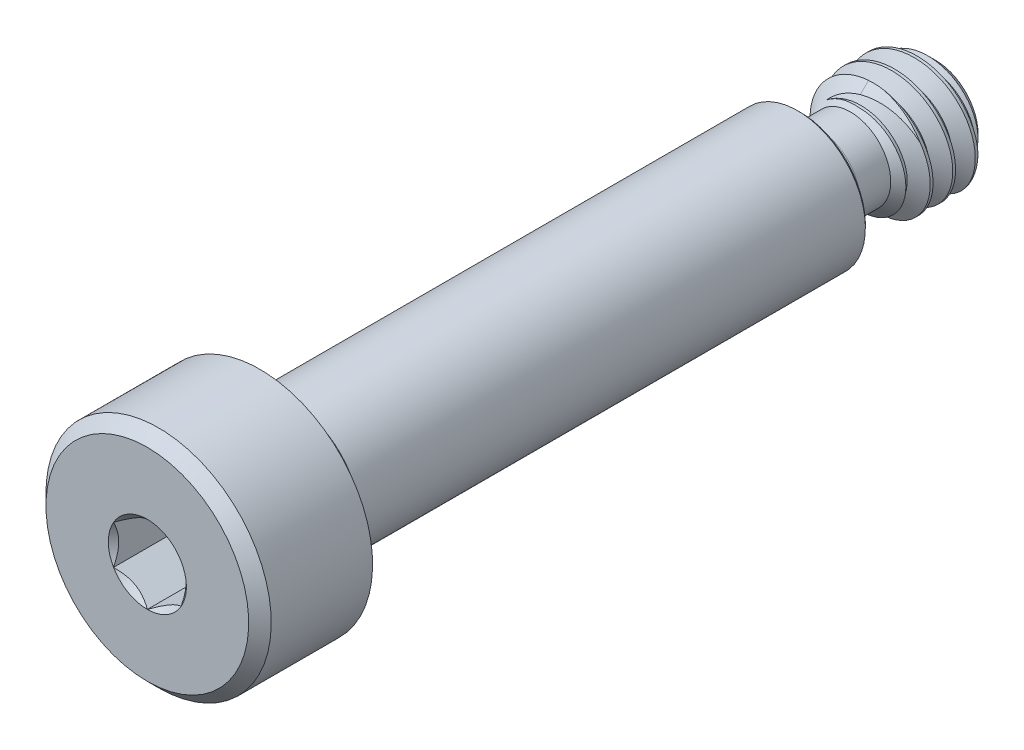
SolidWorks part; units mm, degrees
ref_plane "Front Plane" through (0, 0, 0) normal (0, 0, 1) x (1, 0, 0)
ref_plane "Top Plane" through (0, 0, 0) normal (0, 1, 0) x (1, 0, 0)
ref_plane "Right Plane" through (0, 0, 0) normal (1, 0, 0) x (0, 0, -1)
sketch "Sketch1" plane through (0, 0, 0) normal (1, 0, 0) x (0, 0, -1)
  line L0 (-13.8906, 0) -> (13.8906, 0) construction
  line L1 (-13.8906, 0) -> (-13.8906, 3.9687)
  line L2 (-13.8906, 3.9687) -> (-9.9219, 3.9688)
  line L3 (-9.9219, 3.9688) -> (-9.9219, 2.3813)
  line L4 (-9.9219, 2.3813) -> (9.1281, 2.3813)
  line L5 (9.1281, 2.0828) -> (13.8906, 2.0828)
  line L6 (13.8906, 2.0828) -> (13.8906, 0)
  line L7 (13.841, 2.1687) -> (14.2379, 1.4813) construction
  line L8 (14.2379, 1.4813) -> (14.6348, 2.1687) construction
  line L9 (14.6348, 2.1687) -> (13.841, 2.1687) construction
  line L10 (13.8906, 2.0828) -> (14.5852, 2.0828) construction
  line L11 (14.2379, 2.1687) -> (14.2379, 2.0828) construction
  line L12 (14.2379, 2.0828) -> (14.2379, 1.5672) construction
  line L13 (14.2379, 1.5672) -> (14.2379, 1.4813) construction
  line L14 (14.1883, 1.5672) -> (14.2875, 1.5672)
  line L15 (13.8658, 2.1258) -> (14.61, 2.1258)
  line L16 (14.2875, 1.5672) -> (14.61, 2.1258)
  line L17 (14.1883, 1.5672) -> (13.8658, 2.1258)
  line L18 (13.8906, 0) -> (13.8906, -2.0828) construction
  line L19 (9.1281, -2.3813) -> (9.1281, 0) construction
  line L20 (9.1281, 0) -> (9.1281, 2.3813) construction
  line L21 (-13.8906, 0) -> (-13.8906, -3.9687) construction
  line L22 (9.1281, 2.3813) -> (9.1281, 2.0828)
  line L23 (9.1281, 2.3813) -> (11.8396, 2.3813)
  line L24 (11.8396, 2.3813) -> (10.8807, 1.4224)
  line L25 (10.8807, 1.4224) -> (9.7885, 1.4224)
  arc A0 (9.1281, 2.0828) -> (9.7885, 1.4224) centre (9.7885, 2.0828) ccw
  point P11 (-8.7789, 2.3813)
  point P12 (11.9062, -2.0828)
  point P22 (14.2379, 2.1258)
  point P23 (8.1756, 0)
  point P25 (-8.1756, 0)
  point P26 (-9.9219, -3.9687)
  point P29 (9.1281, -2.3813)
  point P33 (-6.2389, 2.3813)
  point P36 (6.5881, 2.3813)
  dimension "Head Height" = 3.9688
  dimension "Shoulder Diameter" = 4.7625
  dimension "Screw Size Decimal Equivalent" = 4.1656
  dimension "Thread Length" = 4.7625
  dimension "Head Diameter" = 7.9375
  dimension "Undercut Length" = 1.143
  dimension "Pitch" = 0.7937
  dimension "D2" = 0.0992
  dimension "D1" = 1.9844
  dimension "D3" = 5.715
  dimension "D4" = 5.715
  dimension "Shoulder Length" = 19.05
  dimension "Flat OD" = 2.8448
  dimension "Flat" = 1.7526
  dimension "D5" = 45
  dimension "D7" = 2.54
  dimension "D6" = 3.683
sketch "Sketch2" plane through (0, 0, 0) normal (0, 0, 1) x (1, 0, 0)
  line L1 (0, 1.3748) -> (-1.1906, 0.6874)
  line L2 (-1.1906, 0.6874) -> (-1.1906, -0.6874)
  line L3 (-1.1906, -0.6874) -> (0, -1.3748)
  line L4 (0, -1.3748) -> (1.1906, -0.6874)
  line L5 (1.1906, -0.6874) -> (1.1906, 0.6874)
  line L6 (1.1906, 0.6874) -> (0, 1.3748)
  circle A0 centre (0, 0) radius 1.1906 construction
  dimension "Drive Size" = 2.3813
sketch "Sketch4" plane through (0, 0, 0) normal (1, 0, 0) x (0, 0, -1)
  line L0 (-9.9219, 3.9688) -> (-13.4938, 3.9687)
  line L1 (-13.4938, 3.9687) -> (-13.8906, 3.5719)
  line L2 (-9.9219, 3.9688) -> (-9.9219, 2.3813)
  line L3 (-9.9219, 2.3813) -> (-9.8028, 2.2622)
  line L4 (-9.8028, 2.2622) -> (-8.8979, 2.2622)
  line L5 (-8.8979, 2.2622) -> (-8.7789, 2.3813)
  line L6 (-9.9219, 2.3813) -> (9.1281, 2.3813) construction
  line L7 (-13.8906, 0) -> (13.8906, 0) construction
  line L8 (-8.7789, 2.3813) -> (9.0286, 2.3813)
  line L9 (9.0286, 2.3813) -> (9.1281, 2.2818)
  line L10 (9.1281, 2.2818) -> (9.1281, 0)
  line L11 (9.1281, 2.3813) -> (9.1281, 2.2818) construction
  line L12 (9.1281, 2.2818) -> (9.1281, 2.1823) construction
  line L13 (9.1281, 2.1823) -> (9.1281, 2.0828) construction
  line L14 (-13.8906, 3.5719) -> (-13.8906, 0)
  line L15 (-13.8906, 3.9687) -> (-9.9219, 3.9688) construction
  line L16 (-13.8906, 0) -> (9.1281, 0)
  dimension "D1" = 45
  dimension "D2" = 4.5244
  dimension "D3" = 45
  dimension "D4" = 45
  dimension "D5" = 7.1437
revolve "Revolve1" add sketch "Sketch4" angle 360 about L16
sketch "Sketch5" plane through (0, 0, 13.8906) normal (0, 0, 1) x (1, 0, 0)
  line L0 (1.1906, 0.6874) -> (0, 1.3748) construction
  line L1 (1.1906, -0.6874) -> (1.1906, 0.6874) construction
  line L2 (0, -1.3748) -> (1.1906, -0.6874) construction
  line L3 (-1.1906, -0.6874) -> (0, -1.3748) construction
  line L4 (-1.1906, 0.6874) -> (-1.1906, -0.6874) construction
  line L5 (0, 1.3748) -> (-1.1906, 0.6874) construction
  line L6 (1.1906, 0.6874) -> (0, 1.3748)
  line L7 (1.1906, -0.6874) -> (1.1906, 0.6874)
  line L8 (0, -1.3748) -> (1.1906, -0.6874)
  line L9 (-1.1906, -0.6874) -> (0, -1.3748)
  line L10 (-1.1906, 0.6874) -> (-1.1906, -0.6874)
  line L11 (0, 1.3748) -> (-1.1906, 0.6874)
extrude "Cut-Extrude1" cut sketch "Sketch5" against normal blind 2.9766
sketch "Sketch6" plane through (0, 0, 13.8906) normal (0, 0, 1) x (1, 0, 0)
  circle A0 centre (0, 0) radius 1.3748
extrude "Cut-Extrude4" cut sketch "Sketch6" against normal blind 2.9766 draft 45
sketch "Sketch7" plane through (0, 0, 0) normal (1, 0, 0) x (0, 0, -1)
  line L0 (9.1281, 2.0828) -> (13.2953, 2.0828)
  line L1 (9.1281, 2.0828) -> (13.8906, 2.0828) construction
  line L2 (13.2953, 2.0828) -> (13.8906, 1.4875)
  line L3 (13.8906, 2.0828) -> (13.8906, 0) construction
  line L4 (13.8906, 1.4875) -> (13.8906, 0)
  line L5 (13.8906, 0) -> (9.1281, 0)
  line L6 (9.1281, -2.2818) -> (9.1281, 2.2818) construction
  line L7 (9.1281, 0) -> (9.1281, 2.0828)
  dimension "D1" = 45
  dimension "D2" = 0.5953
revolve "Revolve2" add sketch "Sketch7" angle 360 about L5
sketch "Sketch10" plane through (0, 0, 0) normal (1, 0, 0) x (0, 0, -1)
  line L0 (9.7885, 1.4224) -> (10.8807, 1.4224)
  line L1 (10.8807, 1.4224) -> (11.8396, 2.3813)
  line L2 (11.8396, 2.3813) -> (9.1281, 2.3813)
  line L3 (9.1281, 2.3813) -> (9.1281, 2.0828)
  line L4 (9.1281, -2.2818) -> (9.1281, 2.2818) construction
  line L5 (13.8906, 0) -> (9.1281, 0) construction
  line L6 (-13.8906, 0) -> (13.8906, 0) construction
  arc A0 (9.1281, 2.0828) -> (9.7885, 1.4224) centre (9.7885, 2.0828) ccw
revolve "Cut-Revolve1" cut sketch "Sketch10" angle 360 about L5
sketch "Sketch8" plane through (0, 0, -13.8906) normal (0, 0, -1) x (-1, 0, 0)
  circle A0 centre (0, 0) radius 2.0828 construction
  circle A1 centre (0, 0) radius 2.0828
curve "Helix/Spiral1" pitch 0.7937 height 5.5562 radius 2.0828 centre (0, 0, -13.8906) axis (0, 0, 1) start towards (0, 1, 0)
sketch "Sketch9" plane through (0, 0, 0) normal (1, 0, 0) x (0, 0, -1)
  line L0 (14.1883, 1.5672) -> (14.2875, 1.5672) construction
  line L1 (14.2875, 1.5672) -> (14.61, 2.1258) construction
  line L2 (13.8658, 2.1258) -> (14.61, 2.1258) construction
  line L3 (14.1883, 1.5672) -> (13.8658, 2.1258) construction
  line L4 (14.1883, 1.5672) -> (14.2875, 1.5672)
  line L5 (14.2875, 1.5672) -> (14.61, 2.1258)
  line L6 (13.8658, 2.1258) -> (14.61, 2.1258)
  line L7 (14.1883, 1.5672) -> (13.8658, 2.1258)
ref_plane "Plane1" through (0, 0, -10.8807) normal (0, 0, 1) x (1, 0, 0)
split "Split1" trim tools "Plane1" bodies to split 138 resulting bodies 139 140
sweep "Cut-Sweep1" cut profiles "Sketch9" path "Helix/Spiral1" align with end faces yes
combine bodies "Combine1" operation type add bodies to combine 141 139
equation "\"D2@Sketch1\" = \"Pitch@Sketch1\" / 8"
equation "\"D1@Sketch1\" = \"Pitch@Sketch1\" * 2.5"
equation "\"D2@Sketch4\" = \"Shoulder Diameter@Sketch1\" * 0.95"
equation "\"D5@Sketch4\" = \"Head Diameter@Sketch1\" * 0.9"
equation "\"D1@Cut-Extrude1\" = \"Head Height@Sketch1\" * 0.75"
equation "\"D1@Cut-Extrude4\"=\"D1@Cut-Extrude1\""
equation "\"D2@Sketch7\" = \"Pitch@Sketch1\" * 0.75"
equation "\"D3@Helix/Spiral1\" = \"Thread Length@Sketch1\" + \"Pitch@Sketch1\""
equation "\"D4@Helix/Spiral1\" = \"Pitch@Sketch1\""
equation "\"D3@Sketch1\" = \"Thread Length@Sketch1\" * 1.2"
equation "\"D4@Sketch1\" = \"D3@Sketch1\""
equation "\"D6@Sketch1\"=\"Undercut Length@Sketch1\"+.1"
